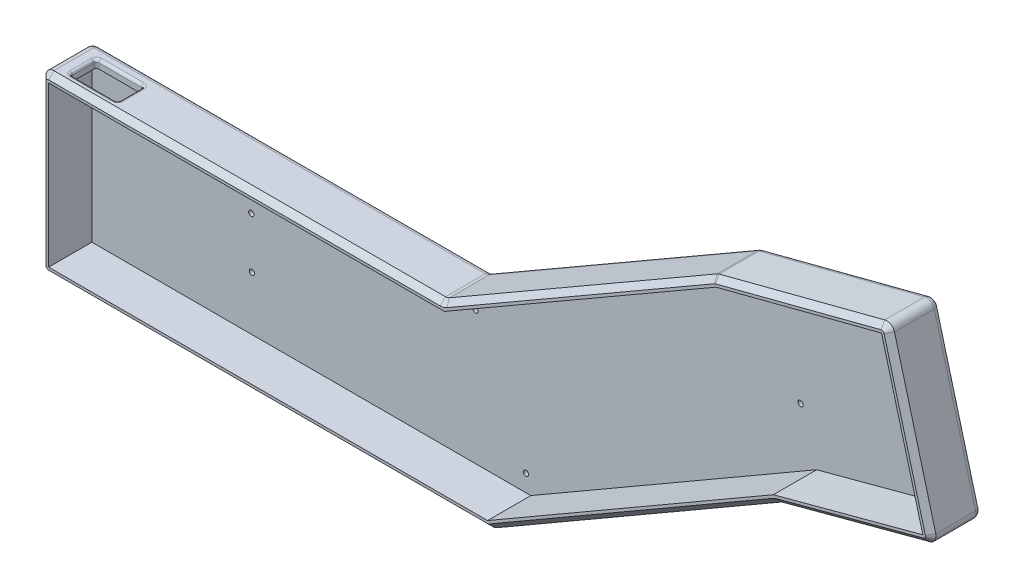
SolidWorks part; units mm, degrees
ref_plane "Plan de face" through (0, 0, 0) normal (0, 0, 1) x (1, 0, 0)
ref_plane "Plan de dessus" through (0, 0, 0) normal (0, 1, 0) x (1, 0, 0)
ref_plane "Plan de droite" through (0, 0, 0) normal (1, 0, 0) x (0, 0, -1)
sketch "Model" plane through (0, 0, 0) normal (0, 0, 1) x (1, 0, 0)
  line L0 (152.8114, 25.9717) -> (138.2826, 80.2215) construction
  line L1 (98.1506, 11.3316) -> (152.8114, 25.9717) construction
  line L2 (-9.3986, -50.8585) -> (98.1506, 11.3316) construction
  line L3 (-172.3739, -50.8585) -> (-9.3986, -50.8585) construction
  line L4 (-24.5886, 5.3017) -> (-172.3739, 5.2915) construction
  line L5 (138.2826, 80.2215) -> (78.0109, 64.5416) construction
  line L6 (-151.6088, 5.3124) -> (-151.6088, 5.2929)
  line L7 (-24.5886, 5.3017) -> (78.0109, 64.5416) construction
  line L8 (-172.3739, 5.2915) -> (-172.3739, -50.6876) construction
  line L9 (-172.3739, -50.6876) -> (-172.3739, -50.8585) construction
  line L10 (-25.1245, 7.3016) -> (-174.3739, 7.2914)
  line L11 (-174.3739, 7.2914) -> (-174.3739, -50.6876)
  line L12 (-174.3739, -50.6876) -> (-174.3739, -52.8585)
  line L13 (-174.3739, -52.8585) -> (-8.862, -52.8585)
  line L14 (-8.862, -52.8585) -> (98.9231, 9.4681)
  line L15 (98.9231, 9.4681) -> (155.2607, 24.5572)
  line L16 (155.2607, 24.5572) -> (139.7008, 82.657)
  line L17 (139.7008, 82.657) -> (77.2454, 66.409)
  line L18 (-25.1245, 7.3016) -> (77.2454, 66.409)
  line L19 (-25.9285, 10.3016) -> (-177.3739, 10.2912)
  line L20 (-177.3739, 10.2912) -> (-177.3739, -50.6876)
  line L21 (-177.3739, -50.6876) -> (-177.3739, -55.8585)
  line L22 (-177.3739, -55.8585) -> (-8.057, -55.8585)
  line L23 (-8.057, -55.8585) -> (100.0819, 6.6727)
  line L24 (100.0819, 6.6727) -> (158.9346, 22.4355)
  line L25 (158.9346, 22.4355) -> (141.8281, 86.3103)
  line L26 (141.8281, 86.3103) -> (76.097, 69.2101)
  line L27 (-25.9285, 10.3016) -> (76.097, 69.2101)
  circle A0 centre (80.6856, 58.4893) radius 1
  circle A1 centre (92.8776, 28.0855) radius 1
  circle A2 centre (-29.7028, -2.6485) radius 1
  circle A3 centre (-10.6528, -46.4381) radius 1
  circle A4 centre (-114.2594, -13.4181) radius 1
  circle A5 centre (-114.0308, -32.4935) radius 1
  dimension "D1" = 2
  dimension "D2" = 3
extrude "Boss.-Extru.1" add sketch "Model" along normal blind 19 contours L27 L19 L20 L21 L22 L23 L24 L25 L26 L10 L18 L17 L16 L15 L14 L13 L12 L11 region at (25.2668, 39.4396, 0)
fillet "Congé1" radius 3 8 edges at (-25.9285, 10.3016, 9.5) (76.097, 69.2101, 9.5) (141.8281, 86.3103, 9.5) (158.9346, 22.4355, 9.5) (100.0819, 6.6727, 9.5) (-8.057, -55.8585, 9.5) (-177.3739, -55.8585, 9.5) (-177.3739, 10.2912, 9.5)
sketch "Esquisse1" plane through (0, 0, 0) normal (0, 0, 1) x (1, 0, 0)
  line L0 (-25.1245, 7.3016) -> (-174.3739, 7.2914) construction
  line L1 (-25.1245, 7.3016) -> (77.2454, 66.409) construction
  line L2 (139.7008, 82.657) -> (77.2454, 66.409) construction
  line L3 (155.2607, 24.5572) -> (139.7008, 82.657) construction
  line L4 (98.9231, 9.4681) -> (155.2607, 24.5572) construction
  line L5 (-8.862, -52.8585) -> (98.9231, 9.4681) construction
  line L6 (-174.3739, -52.8585) -> (-8.862, -52.8585) construction
  line L7 (-174.3739, -50.6876) -> (-174.3739, -52.8585) construction
  line L8 (-174.3739, 7.2914) -> (-174.3739, -50.6876) construction
  line L9 (-25.1245, 7.3016) -> (-174.3739, 7.2914)
  line L10 (-25.1245, 7.3016) -> (77.2454, 66.409)
  line L11 (139.7008, 82.657) -> (77.2454, 66.409)
  line L12 (155.2607, 24.5572) -> (139.7008, 82.657)
  line L13 (98.9231, 9.4681) -> (155.2607, 24.5572)
  line L14 (-8.862, -52.8585) -> (98.9231, 9.4681)
  line L15 (-174.3739, -52.8585) -> (-8.862, -52.8585)
  line L16 (-174.3739, -50.6876) -> (-174.3739, -52.8585)
  line L17 (-174.3739, 7.2914) -> (-174.3739, -50.6876)
  circle A0 centre (-114.2594, -13.4181) radius 1 construction
  circle A1 centre (-114.2594, -13.4181) radius 1
  circle A2 centre (-114.0308, -32.4935) radius 1 construction
  circle A3 centre (-114.0308, -32.4935) radius 1
  circle A4 centre (-29.7028, -2.6485) radius 1 construction
  circle A5 centre (-29.7028, -2.6485) radius 1
  circle A6 centre (-10.6528, -46.4381) radius 1 construction
  circle A7 centre (-10.6528, -46.4381) radius 1
  circle A8 centre (80.6856, 58.4893) radius 1 construction
  circle A9 centre (80.6856, 58.4893) radius 1
  circle A10 centre (92.8776, 28.0855) radius 1 construction
  circle A11 centre (92.8776, 28.0855) radius 1
extrude "Boss.-Extru.2" add sketch "Esquisse1" along normal blind 2.7
sketch "Esquisse2" plane through (0, 0, 0) normal (0, 0, -1) x (-1, 0, 0)
  circle A0 centre (-80.6856, 58.4893) radius 1 construction
  circle A1 centre (-92.8776, 28.0855) radius 1 construction
  circle A2 centre (29.7028, -2.6485) radius 1 construction
  circle A3 centre (10.6528, -46.4381) radius 1 construction
  circle A4 centre (114.2594, -13.4181) radius 1 construction
  circle A5 centre (114.0308, -32.4935) radius 1 construction
  circle A6 centre (-80.6856, 58.4893) radius 1
  circle A7 centre (-92.8776, 28.0855) radius 1
  circle A8 centre (29.7028, -2.6485) radius 1
  circle A9 centre (10.6528, -46.4381) radius 1
  circle A10 centre (114.2594, -13.4181) radius 1
  circle A11 centre (114.0308, -32.4935) radius 1
  circle A12 centre (-80.6856, 58.4893) radius 2
  circle A13 centre (-92.8776, 28.0855) radius 2
  circle A14 centre (29.7028, -2.6485) radius 2
  circle A15 centre (10.6528, -46.4381) radius 2
  circle A16 centre (114.2594, -13.4181) radius 2
  circle A17 centre (114.0308, -32.4935) radius 2
  dimension "D1" = 1
extrude "Enlèv. mat.-Extru.1" cut sketch "Esquisse2" against normal blind 1
chamfer "Chanfrein1" distance 2 angle 45 16 edges at (141.2104, 85.2495, 19) (150.3786, 54.3832, 19) (157.8586, 23.0569, 19) (128.2507, 14.2173, 19) (100.0919, 6.6486, 19) (46.1894, -24.4906, 19) (-8.0845, -55.756, 19) (-91.6179, -55.8585, 19) (-176.4952, -54.9798, 19) (-177.3739, -22.7836, 19) (-176.4953, 9.4126, 19) (-100.5532, 10.2965, 19) (-25.9559, 10.4038, 19) (25.2564, 39.8553, 19) (76.1074, 69.1848, 19) (107.7178, 77.4364, 19)
fillet "Congé2" radius 2 16 edges at (100.0919, 6.6486, 0) (46.1894, -24.4906, 0) (-8.0845, -55.756, 0) (-91.6179, -55.8585, 0) (-176.4952, -54.9798, 0) (-177.3739, -22.7836, 0) (-176.4953, 9.4126, 0) (-100.5532, 10.2965, 0) (-25.9559, 10.4038, 0) (25.2564, 39.8553, 0) (76.1074, 69.1848, 0) (107.7178, 77.4364, 0) (141.2104, 85.2495, 0) (150.3786, 54.3832, 0) (157.8586, 23.0569, 0) (128.2507, 14.2173, 0)
sketch "Esquisse3" plane through (-0.0007, 10.3034, 0) normal (-0.0001, 1, 0) x (1, 0.0001, 0)
  line L0 (-174.3734, -2) -> (-174.3734, -17) construction
  line L1 (-169.3734, -5) -> (-153.3734, -5)
  line L2 (-170.3734, -6) -> (-170.3734, -14)
  line L3 (-169.3734, -15) -> (-153.3734, -15)
  line L4 (-152.3734, -6) -> (-152.3734, -14)
  line L5 (-26.7316, -2) -> (-174.3734, -2) construction
  arc A0 (-170.3734, -14) -> (-169.3734, -15) centre (-169.3734, -14) ccw
  arc A1 (-153.3734, -15) -> (-152.3734, -14) centre (-153.3734, -14) ccw
  arc A2 (-153.3734, -5) -> (-152.3734, -6) centre (-153.3734, -6) cw
  arc A3 (-169.3734, -5) -> (-170.3734, -6) centre (-169.3734, -6) ccw
  point P10 (-170.3734, -15)
  point P13 (-152.3734, -15)
  point P16 (-152.3734, -5)
  dimension "D5" = 1
  dimension "D1" = 4
  dimension "D2" = 18
  dimension "D3" = 10
  dimension "D4" = 3
extrude "Enlèv. mat.-Extru.2" cut sketch "Esquisse3" against normal blind 10
fillet "Congé3" radius 1 8 edges at (-152.667, 10.2929, 5.2929) (-152.3741, 10.2929, 10) (-152.667, 10.2929, 14.7071) (-161.3741, 10.2923, 15) (-170.0812, 10.2917, 14.7071) (-170.3741, 10.2917, 10) (-170.0812, 10.2917, 5.2929) (-161.3741, 10.2923, 5)
